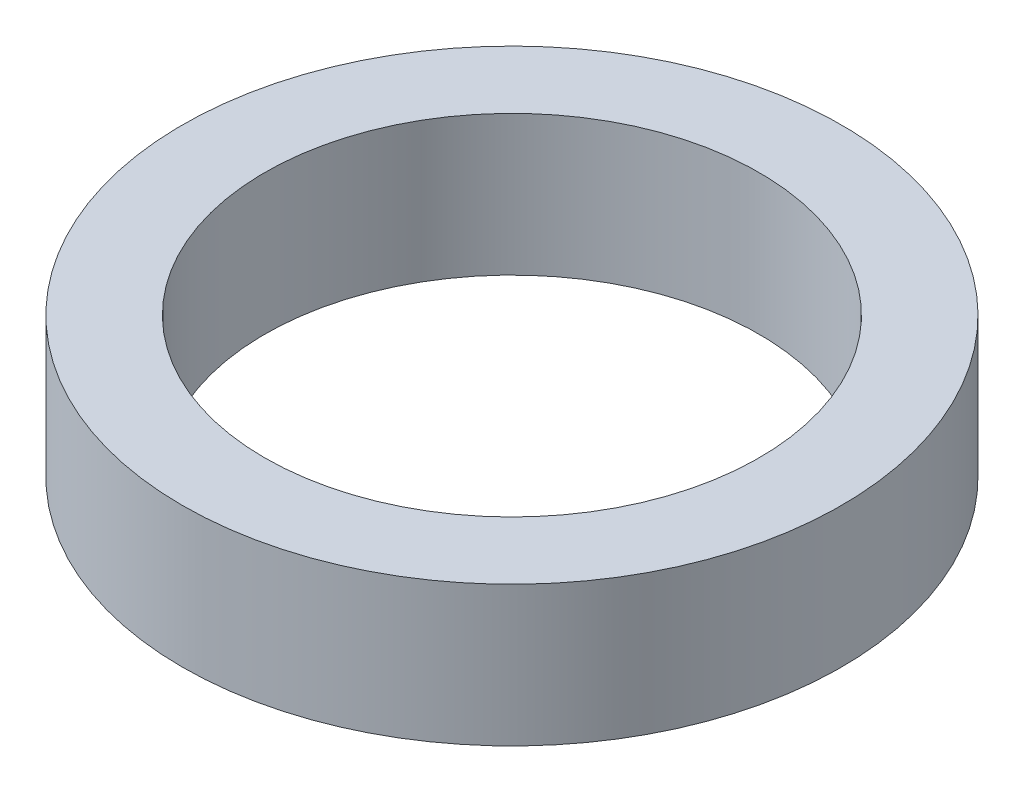
SolidWorks part; units mm, degrees
ref_plane "Front Plane" through (0, 0, 0) normal (0, 0, 1) x (1, 0, 0)
ref_plane "Top Plane" through (0, 0, 0) normal (0, 1, 0) x (1, 0, 0)
ref_plane "Right Plane" through (0, 0, 0) normal (1, 0, 0) x (0, 0, -1)
sketch "Sketch1" plane through (0, 0, 0) normal (0, 1, 0) x (1, 0, 0)
  circle A0 centre (0, 0) radius 40
  dimension "FLANGE_OD" = 80
extrude "Boss-Extrude1" add sketch "Sketch1" along normal blind 17
sketch "Sketch2" plane through (0, 0, 0) normal (0, 1, 0) x (1, 0, 0)
  circle A0 centre (0, 0) radius 30
  dimension "BORE_D" = 60
extrude "Cut-Extrude1" cut sketch "Sketch2" along normal through all
sketch "Sketch3" plane through (0, 17, 0) normal (0, 1, 0) x (1, 0, 0)
  circle A0 centre (0, 0) radius 17.3987 construction
  circle A1 centre (-17.3987, 0) radius 1.5984
  dimension "BOLT_D" = 3.1967
  dimension "BOLT_PCD" = 34.7975
extrude "Cut-Extrude2" cut sketch "Sketch3" against normal blind 13.0136 rebuild error yes
pattern_circular "CirPattern1" count 6 over 360 rebuild error yes
